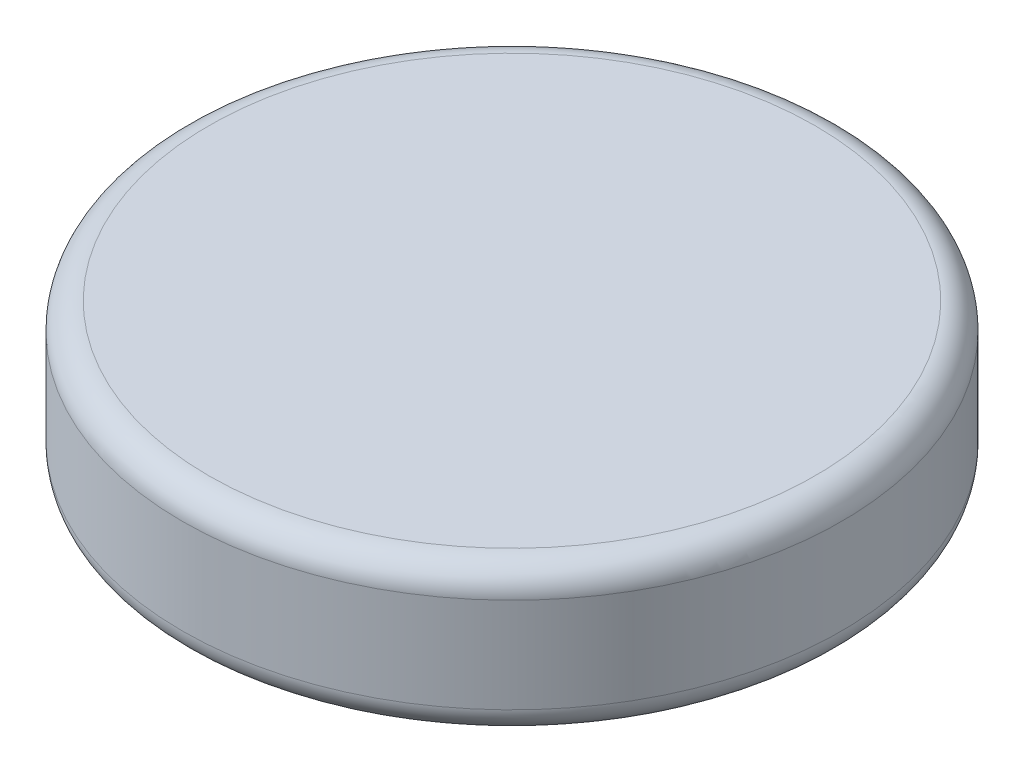
SolidWorks part; units mm, degrees
ref_plane "Front Plane" through (0, 0, 0) normal (0, 0, 1) x (1, 0, 0)
ref_plane "Top Plane" through (0, 0, 0) normal (0, 1, 0) x (1, 0, 0)
ref_plane "Right Plane" through (0, 0, 0) normal (1, 0, 0) x (0, 0, -1)
sketch "Sketch1" plane through (0, 0, 0) normal (0, 1, 0) x (1, 0, 0)
  circle A0 centre (0, 0) radius 15.875
  dimension "D1" = 31.75
extrude "Boss-Extrude1" add sketch "Sketch1" along normal blind 7.112 contours A0
fillet "Fillet1" radius 1.27 2 edges at (0, 0, 15.875) (0, 7.112, 15.875)
